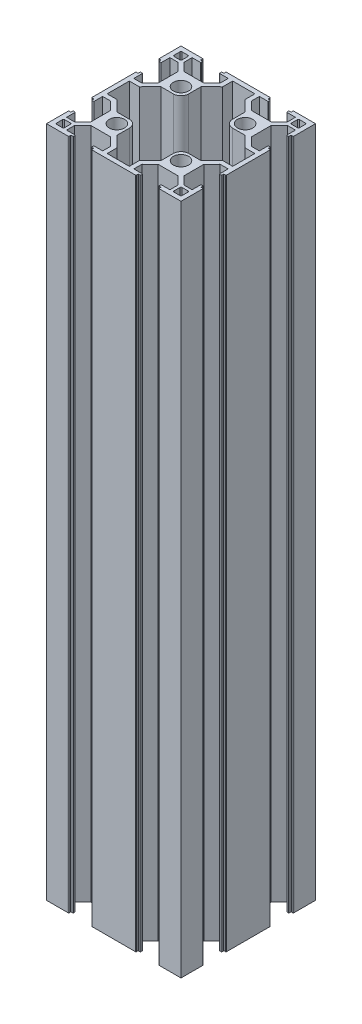
SolidWorks part; units mm, degrees
ref_plane "Front Plane" through (0, 0, 0) normal (0, 0, 1) x (1, 0, 0)
ref_plane "Top Plane" through (0, 0, 0) normal (0, 1, 0) x (1, 0, 0)
ref_plane "Right Plane" through (0, 0, 0) normal (1, 0, 0) x (0, 0, -1)
sketch "Sketch1" plane through (0, 0, 0) normal (0, 1, 0) x (1, 0, 0)
  line L0 (0, 30) -> (0, -30) construction
  line L1 (-30, -30) -> (30, -30)
  line L2 (-30, -30) -> (-30, 30)
  line L3 (-30, 30) -> (30, 30)
  line L4 (30, -30) -> (30, 30)
  line L5 (-30, -30) -> (30, 30) construction
  line L6 (-30, 30) -> (30, -30) construction
  line L7 (-30, 0) -> (30, 0) construction
  line L8 (-23.05, -28) -> (-6.95, -28)
  line L9 (-6.95, -28) -> (-6.95, -24.4)
  line L10 (-6.95, -24.4) -> (-10.615, -20.8)
  line L11 (-10.615, -20.8) -> (-19.385, -20.8)
  line L12 (-19.385, -20.8) -> (-23.05, -24.4)
  line L13 (-23.05, -24.4) -> (-23.05, -28)
  line L14 (10.615, -20.8) -> (19.385, -20.8)
  line L15 (6.95, -24.4) -> (10.615, -20.8)
  line L16 (6.95, -28) -> (6.95, -24.4)
  line L17 (23.05, -28) -> (6.95, -28)
  line L18 (23.05, -24.4) -> (23.05, -28)
  line L19 (19.385, -20.8) -> (23.05, -24.4)
  line L20 (19.385, 20.8) -> (23.05, 24.4)
  line L21 (23.05, 24.4) -> (23.05, 28)
  line L22 (23.05, 28) -> (6.95, 28)
  line L23 (6.95, 28) -> (6.95, 24.4)
  line L24 (6.95, 24.4) -> (10.615, 20.8)
  line L25 (10.615, 20.8) -> (19.385, 20.8)
  line L26 (-23.05, 24.4) -> (-23.05, 28)
  line L27 (-19.385, 20.8) -> (-23.05, 24.4)
  line L28 (-10.615, 20.8) -> (-19.385, 20.8)
  line L29 (-6.95, 24.4) -> (-10.615, 20.8)
  line L30 (-6.95, 28) -> (-6.95, 24.4)
  line L31 (-23.05, 28) -> (-6.95, 28)
  line L32 (-20.8, 19.385) -> (-24.4, 23.05)
  line L33 (-24.4, 23.05) -> (-28, 23.05)
  line L34 (-28, 23.05) -> (-28, 6.95)
  line L35 (-28, 6.95) -> (-24.4, 6.95)
  line L36 (-24.4, 6.95) -> (-20.8, 10.615)
  line L37 (-20.8, 10.615) -> (-20.8, 19.385)
  line L38 (-24.4, -23.05) -> (-28, -23.05)
  line L39 (-20.8, -19.385) -> (-24.4, -23.05)
  line L40 (-20.8, -10.615) -> (-20.8, -19.385)
  line L41 (-24.4, -6.95) -> (-20.8, -10.615)
  line L42 (-28, -6.95) -> (-24.4, -6.95)
  line L43 (-28, -23.05) -> (-28, -6.95)
  line L44 (20.8, -19.385) -> (24.4, -23.05)
  line L45 (24.4, -23.05) -> (28, -23.05)
  line L46 (28, -23.05) -> (28, -6.95)
  line L47 (28, -6.95) -> (24.4, -6.95)
  line L48 (24.4, -6.95) -> (20.8, -10.615)
  line L49 (20.8, -10.615) -> (20.8, -19.385)
  line L50 (24.4, 23.05) -> (28, 23.05)
  line L51 (20.8, 19.385) -> (24.4, 23.05)
  line L52 (20.8, 10.615) -> (20.8, 19.385)
  line L53 (24.4, 6.95) -> (20.8, 10.615)
  line L54 (28, 6.95) -> (24.4, 6.95)
  line L55 (28, 23.05) -> (28, 6.95)
  point P0 (0, 0)
  dimension "D1" = 60
  dimension "D2" = 16.1
  dimension "D3" = 8.77
  dimension "D4" = 3.6
  dimension "D5" = 7.2
  dimension "D6" = 2
  dimension "D7" = 6.95
extrude "Boss-Extrude1" add sketch "Sketch1" along normal blind 300
sketch "Sketch2" plane through (0, 300, 0) normal (0, 1, 0) x (1, 0, 0)
  line L0 (-19.1, -28) -> (-19.1, -29)
  line L1 (-23.05, -28) -> (-6.95, -28) construction
  line L2 (-30, -30) -> (30, -30) construction
  line L3 (-10.9, -28) -> (-10.9, -29)
  line L4 (-10.9, -29) -> (-9.9, -29)
  line L5 (-9.9, -29) -> (-9.9, -30)
  line L6 (-19.1, -29) -> (-20.1, -29)
  line L7 (-20.1, -29) -> (-20.1, -30)
  line L8 (-19.1, -28) -> (-10.9, -28)
  line L9 (-20.1, -30) -> (-9.9, -30)
  dimension "D1" = 8.2
  dimension "D2" = 3.95
  dimension "D3" = 1
  dimension "D4" = 1
extrude "Cut-Extrude1" cut sketch "Sketch2" against normal through all
mirror "Mirror1" about plane through (0, 0, 0) normal (1, 0, 0) of "Cut-Extrude1"
ref_axis "Axis1" through (0, 1050, 0) along (0, -1, 0)
pattern_circular "CirPattern1" count 4 over 360 about axis through (0, 1050, 0) along (0, -1, 0) of "Cut-Extrude1", "Mirror1"
sketch "Sketch4" plane through (0, 300, 0) normal (0, 1, 0) x (1, 0, 0)
  line L0 (19.385, 18.8) -> (9.797, 18.8) construction
  line L1 (-18.8, 18.8) -> (-18.8, 9.797)
  line L2 (18.8, -19.385) -> (18.8, -9.797) construction
  line L3 (28, 4.95) -> (28, -4.95)
  line L4 (-18.8, -9.797) -> (-18.8, -19.385) construction
  line L5 (4.95, -28) -> (-4.95, -28)
  line L6 (-9.797, 18.8) -> (-9.797, 13.197)
  line L7 (-28, -4.95) -> (-28, 4.95)
  line L8 (-18.8, 9.797) -> (-23.5611, 4.95)
  line L9 (-23.5611, 4.95) -> (-28, 4.95)
  line L10 (18.8, 18.8) -> (9.797, 18.8)
  line L11 (9.797, 18.8) -> (4.95, 23.5611)
  line L12 (4.95, 23.5611) -> (4.95, 28)
  line L13 (4.95, 28) -> (4.95, 28)
  line L14 (4.95, 28) -> (4.95, 28)
  line L15 (4.95, 28) -> (4.95, 28)
  line L16 (4.95, 28) -> (4.95, 28)
  line L17 (4.95, 28) -> (-4.95, 28)
  line L18 (-4.95, 28) -> (-4.95, 28)
  line L19 (-4.95, 28) -> (-4.95, 28)
  line L20 (-4.95, 28) -> (-4.95, 28)
  line L21 (-4.95, 28) -> (-4.95, 28)
  line L22 (-4.95, 28) -> (-4.95, 23.5611)
  line L23 (-4.95, 23.5611) -> (-9.797, 18.8)
  line L24 (-9.797, 18.8) -> (-18.8, 18.8)
  line L25 (28, 4.95) -> (23.5611, 4.95)
  line L26 (23.5611, 4.95) -> (18.8, 9.797)
  line L27 (18.8, 9.797) -> (18.8, 18.8)
  line L28 (18.8, -18.8) -> (18.8, -9.797)
  line L29 (18.8, -9.797) -> (23.5611, -4.95)
  line L30 (23.5611, -4.95) -> (28, -4.95)
  line L31 (4.95, -28) -> (4.95, -23.5611)
  line L32 (4.95, -23.5611) -> (9.797, -18.8)
  line L33 (9.797, -18.8) -> (18.8, -18.8)
  line L34 (-18.8, -18.8) -> (-9.797, -18.8)
  line L35 (-9.797, -18.8) -> (-4.95, -23.5611)
  line L36 (-4.95, -23.5611) -> (-4.95, -28)
  line L37 (-28, -4.95) -> (-23.5611, -4.95)
  line L38 (-23.5611, -4.95) -> (-18.8, -9.797)
  line L39 (-18.8, -9.797) -> (-18.8, -18.8)
  line L40 (-9.797, 18.8) -> (-19.385, 18.8) construction
  line L41 (-18.8, 19.385) -> (-18.8, 9.797) construction
  line L42 (18.8, 9.797) -> (18.8, 19.385) construction
  line L43 (9.797, -18.8) -> (19.385, -18.8) construction
  line L44 (-19.385, -18.8) -> (-9.797, -18.8) construction
  line L45 (-13.197, 9.797) -> (-18.8, 9.797)
  line L46 (9.797, 18.8) -> (9.797, 13.197)
  line L47 (13.197, 9.797) -> (18.8, 9.797)
  line L48 (-18.8, -9.797) -> (-13.197, -9.797)
  line L49 (-9.797, -13.197) -> (-9.797, -18.8)
  line L50 (9.797, -18.8) -> (9.797, -13.197)
  line L51 (13.197, -9.797) -> (18.8, -9.797)
  line L52 (-27.5, -28) -> (-24.9, -28)
  line L53 (24.9, -28) -> (27.5, -28)
  line L54 (24.4, -27.5) -> (24.4, -24.9)
  line L55 (24.9, -24.4) -> (27.5, -24.4)
  line L56 (28, -27.5) -> (28, -24.9)
  line L57 (24.4, -28) -> (28, -24.4) construction
  line L58 (24.4, -24.4) -> (28, -28) construction
  line L59 (-28, -24.9) -> (-28, -27.5)
  line L60 (-27.5, -24.4) -> (-24.9, -24.4)
  line L61 (-24.4, -24.9) -> (-24.4, -27.5)
  line L62 (-28, 27.5) -> (-28, 24.9)
  line L63 (-24.9, 28) -> (-27.5, 28)
  line L64 (-24.4, 27.5) -> (-24.4, 24.9)
  line L65 (-24.9, 24.4) -> (-27.5, 24.4)
  line L66 (27.5, 28) -> (24.9, 28)
  line L67 (28, 24.9) -> (28, 27.5)
  line L68 (27.5, 24.4) -> (24.9, 24.4)
  line L69 (24.4, 24.9) -> (24.4, 27.5)
  line L116 (28, 19.1) -> (29, 19.1)
  line L117 (29, 19.1) -> (29, 20.1)
  line L118 (29, 20.1) -> (30, 20.1)
  line L119 (30, 20.1) -> (30, 30)
  line L120 (30, 30) -> (20.1, 30)
  line L121 (20.1, 30) -> (20.1, 29)
  line L122 (20.1, 29) -> (19.1, 29)
  line L123 (19.1, 29) -> (19.1, 28)
  line L124 (19.1, 28) -> (23.05, 28)
  line L125 (23.05, 28) -> (23.05, 24.4)
  line L126 (23.05, 24.4) -> (19.385, 20.8)
  line L127 (19.385, 20.8) -> (10.615, 20.8)
  line L128 (10.615, 20.8) -> (6.95, 24.4)
  line L129 (6.95, 24.4) -> (6.95, 28)
  line L130 (6.95, 28) -> (10.9, 28)
  line L131 (10.9, 28) -> (10.9, 29)
  line L132 (10.9, 29) -> (9.9, 29)
  line L133 (9.9, 29) -> (9.9, 30)
  line L134 (9.9, 30) -> (-9.9, 30)
  line L135 (-9.9, 30) -> (-9.9, 29)
  line L136 (-9.9, 29) -> (-10.9, 29)
  line L137 (-10.9, 29) -> (-10.9, 28)
  line L138 (-10.9, 28) -> (-6.95, 28)
  line L139 (-6.95, 28) -> (-6.95, 24.4)
  line L140 (-6.95, 24.4) -> (-10.615, 20.8)
  line L141 (-10.615, 20.8) -> (-19.385, 20.8)
  line L142 (-19.385, 20.8) -> (-23.05, 24.4)
  line L143 (-23.05, 24.4) -> (-23.05, 28)
  line L144 (-23.05, 28) -> (-19.1, 28)
  line L145 (-19.1, 28) -> (-19.1, 29)
  line L146 (-19.1, 29) -> (-20.1, 29)
  line L147 (-20.1, 29) -> (-20.1, 30)
  line L148 (-20.1, 30) -> (-30, 30)
  line L149 (-30, 30) -> (-30, 20.1)
  line L150 (-30, 20.1) -> (-29, 20.1)
  line L151 (-29, 20.1) -> (-29, 19.1)
  line L152 (-29, 19.1) -> (-28, 19.1)
  line L153 (-28, 19.1) -> (-28, 23.05)
  line L154 (-28, 23.05) -> (-24.4, 23.05)
  line L155 (-24.4, 23.05) -> (-20.8, 19.385)
  line L156 (-20.8, 19.385) -> (-20.8, 10.615)
  line L157 (-20.8, 10.615) -> (-24.4, 6.95)
  line L158 (-24.4, 6.95) -> (-28, 6.95)
  line L159 (-28, 6.95) -> (-28, 10.9)
  line L160 (-28, 10.9) -> (-29, 10.9)
  line L161 (-29, 10.9) -> (-29, 9.9)
  line L162 (-29, 9.9) -> (-30, 9.9)
  line L163 (-30, 9.9) -> (-30, -9.9)
  line L164 (-30, -9.9) -> (-29, -9.9)
  line L165 (-29, -9.9) -> (-29, -10.9)
  line L166 (-29, -10.9) -> (-28, -10.9)
  line L167 (-28, -10.9) -> (-28, -6.95)
  line L168 (-28, -6.95) -> (-24.4, -6.95)
  line L169 (-24.4, -6.95) -> (-20.8, -10.615)
  line L170 (-20.8, -10.615) -> (-20.8, -19.385)
  line L171 (-20.8, -19.385) -> (-24.4, -23.05)
  line L172 (-24.4, -23.05) -> (-28, -23.05)
  line L173 (-28, -23.05) -> (-28, -19.1)
  line L174 (-28, -19.1) -> (-29, -19.1)
  line L175 (-29, -19.1) -> (-29, -20.1)
  line L176 (-29, -20.1) -> (-30, -20.1)
  line L177 (-30, -20.1) -> (-30, -30)
  line L178 (-30, -30) -> (-20.1, -30)
  line L179 (-20.1, -30) -> (-20.1, -29)
  line L180 (-20.1, -29) -> (-19.1, -29)
  line L181 (-19.1, -29) -> (-19.1, -28)
  line L182 (-19.1, -28) -> (-23.05, -28)
  line L183 (-23.05, -28) -> (-23.05, -24.4)
  line L184 (-23.05, -24.4) -> (-19.385, -20.8)
  line L185 (-19.385, -20.8) -> (-10.615, -20.8)
  line L186 (-10.615, -20.8) -> (-6.95, -24.4)
  line L187 (-6.95, -24.4) -> (-6.95, -28)
  line L188 (-6.95, -28) -> (-10.9, -28)
  line L189 (-10.9, -28) -> (-10.9, -29)
  line L190 (-10.9, -29) -> (-9.9, -29)
  line L191 (-9.9, -29) -> (-9.9, -30)
  line L192 (-9.9, -30) -> (9.9, -30)
  line L193 (9.9, -30) -> (9.9, -29)
  line L194 (9.9, -29) -> (10.9, -29)
  line L195 (10.9, -29) -> (10.9, -28)
  line L196 (10.9, -28) -> (6.95, -28)
  line L197 (6.95, -28) -> (6.95, -24.4)
  line L198 (6.95, -24.4) -> (10.615, -20.8)
  line L199 (10.615, -20.8) -> (19.385, -20.8)
  line L200 (19.385, -20.8) -> (23.05, -24.4)
  line L201 (23.05, -24.4) -> (23.05, -28)
  line L202 (23.05, -28) -> (19.1, -28)
  line L203 (19.1, -28) -> (19.1, -29)
  line L204 (19.1, -29) -> (20.1, -29)
  line L205 (20.1, -29) -> (20.1, -30)
  line L206 (20.1, -30) -> (30, -30)
  line L207 (30, -30) -> (30, -20.1)
  line L208 (30, -20.1) -> (29, -20.1)
  line L209 (29, -20.1) -> (29, -19.1)
  line L210 (29, -19.1) -> (28, -19.1)
  line L211 (28, -19.1) -> (28, -23.05)
  line L212 (28, -23.05) -> (24.4, -23.05)
  line L213 (24.4, -23.05) -> (20.8, -19.385)
  line L214 (20.8, -19.385) -> (20.8, -10.615)
  line L215 (20.8, -10.615) -> (24.4, -6.95)
  line L216 (24.4, -6.95) -> (28, -6.95)
  line L217 (28, -6.95) -> (28, -10.9)
  line L218 (28, -10.9) -> (29, -10.9)
  line L219 (29, -10.9) -> (29, -9.9)
  line L220 (29, -9.9) -> (30, -9.9)
  line L221 (30, -9.9) -> (30, 9.9)
  line L222 (30, 9.9) -> (29, 9.9)
  line L223 (29, 9.9) -> (29, 10.9)
  line L224 (29, 10.9) -> (28, 10.9)
  line L225 (28, 10.9) -> (28, 6.95)
  line L226 (28, 6.95) -> (24.4, 6.95)
  line L227 (24.4, 6.95) -> (20.8, 10.615)
  line L228 (20.8, 10.615) -> (20.8, 19.385)
  line L229 (20.8, 19.385) -> (24.4, 23.05)
  line L230 (24.4, 23.05) -> (28, 23.05)
  line L231 (28, 23.05) -> (28, 19.1)
  line L232 (28, 19.1) -> (29, 19.1)
  line L233 (29, 19.1) -> (29, 20.1)
  line L234 (29, 20.1) -> (30, 20.1)
  line L235 (30, 20.1) -> (30, 30)
  line L236 (30, 30) -> (20.1, 30)
  line L237 (20.1, 30) -> (20.1, 29)
  line L238 (20.1, 29) -> (19.1, 29)
  line L239 (19.1, 29) -> (19.1, 28)
  line L240 (19.1, 28) -> (23.05, 28)
  line L241 (23.05, 28) -> (23.05, 24.4)
  line L242 (23.05, 24.4) -> (19.385, 20.8)
  line L243 (19.385, 20.8) -> (10.615, 20.8)
  line L244 (10.615, 20.8) -> (6.95, 24.4)
  line L245 (6.95, 24.4) -> (6.95, 28)
  line L246 (6.95, 28) -> (10.9, 28)
  line L247 (10.9, 28) -> (10.9, 29)
  line L248 (10.9, 29) -> (9.9, 29)
  line L249 (9.9, 29) -> (9.9, 30)
  line L250 (9.9, 30) -> (-9.9, 30)
  line L251 (-9.9, 30) -> (-9.9, 29)
  line L252 (-9.9, 29) -> (-10.9, 29)
  line L253 (-10.9, 29) -> (-10.9, 28)
  line L254 (-10.9, 28) -> (-6.95, 28)
  line L255 (-6.95, 28) -> (-6.95, 24.4)
  line L256 (-6.95, 24.4) -> (-10.615, 20.8)
  line L257 (-10.615, 20.8) -> (-19.385, 20.8)
  line L258 (-19.385, 20.8) -> (-23.05, 24.4)
  line L259 (-23.05, 24.4) -> (-23.05, 28)
  line L260 (-23.05, 28) -> (-19.1, 28)
  line L261 (-19.1, 28) -> (-19.1, 29)
  line L262 (-19.1, 29) -> (-20.1, 29)
  line L263 (-20.1, 29) -> (-20.1, 30)
  line L264 (-20.1, 30) -> (-30, 30)
  line L265 (-30, 30) -> (-30, 20.1)
  line L266 (-30, 20.1) -> (-29, 20.1)
  line L267 (-29, 20.1) -> (-29, 19.1)
  line L268 (-29, 19.1) -> (-28, 19.1)
  line L269 (-28, 19.1) -> (-28, 23.05)
  line L270 (-28, 23.05) -> (-24.4, 23.05)
  line L271 (-24.4, 23.05) -> (-20.8, 19.385)
  line L272 (-20.8, 19.385) -> (-20.8, 10.615)
  line L273 (-20.8, 10.615) -> (-24.4, 6.95)
  line L274 (-24.4, 6.95) -> (-28, 6.95)
  line L275 (-28, 6.95) -> (-28, 10.9)
  line L276 (-28, 10.9) -> (-29, 10.9)
  line L277 (-29, 10.9) -> (-29, 9.9)
  line L278 (-29, 9.9) -> (-30, 9.9)
  line L279 (-30, 9.9) -> (-30, -9.9)
  line L280 (-30, -9.9) -> (-29, -9.9)
  line L281 (-29, -9.9) -> (-29, -10.9)
  line L282 (-29, -10.9) -> (-28, -10.9)
  line L283 (-28, -10.9) -> (-28, -6.95)
  line L284 (-28, -6.95) -> (-24.4, -6.95)
  line L285 (-24.4, -6.95) -> (-20.8, -10.615)
  line L286 (-20.8, -10.615) -> (-20.8, -19.385)
  line L287 (-20.8, -19.385) -> (-24.4, -23.05)
  line L288 (-24.4, -23.05) -> (-28, -23.05)
  line L289 (-28, -23.05) -> (-28, -19.1)
  line L290 (-28, -19.1) -> (-29, -19.1)
  line L291 (-29, -19.1) -> (-29, -20.1)
  line L292 (-29, -20.1) -> (-30, -20.1)
  line L293 (-30, -20.1) -> (-30, -30)
  line L294 (-30, -30) -> (-20.1, -30)
  line L295 (-20.1, -30) -> (-20.1, -29)
  line L296 (-20.1, -29) -> (-19.1, -29)
  line L297 (-19.1, -29) -> (-19.1, -28)
  line L298 (-19.1, -28) -> (-23.05, -28)
  line L299 (-23.05, -28) -> (-23.05, -24.4)
  line L300 (-23.05, -24.4) -> (-19.385, -20.8)
  line L301 (-19.385, -20.8) -> (-10.615, -20.8)
  line L302 (-10.615, -20.8) -> (-6.95, -24.4)
  line L303 (-6.95, -24.4) -> (-6.95, -28)
  line L304 (-6.95, -28) -> (-10.9, -28)
  line L305 (-10.9, -28) -> (-10.9, -29)
  line L306 (-10.9, -29) -> (-9.9, -29)
  line L307 (-9.9, -29) -> (-9.9, -30)
  line L308 (-9.9, -30) -> (9.9, -30)
  line L309 (9.9, -30) -> (9.9, -29)
  line L310 (9.9, -29) -> (10.9, -29)
  line L311 (10.9, -29) -> (10.9, -28)
  line L312 (10.9, -28) -> (6.95, -28)
  line L313 (6.95, -28) -> (6.95, -24.4)
  line L314 (6.95, -24.4) -> (10.615, -20.8)
  line L315 (10.615, -20.8) -> (19.385, -20.8)
  line L316 (19.385, -20.8) -> (23.05, -24.4)
  line L317 (23.05, -24.4) -> (23.05, -28)
  line L318 (23.05, -28) -> (19.1, -28)
  line L319 (19.1, -28) -> (19.1, -29)
  line L320 (19.1, -29) -> (20.1, -29)
  line L321 (20.1, -29) -> (20.1, -30)
  line L322 (20.1, -30) -> (30, -30)
  line L323 (30, -30) -> (30, -20.1)
  line L324 (30, -20.1) -> (29, -20.1)
  line L325 (29, -20.1) -> (29, -19.1)
  line L326 (29, -19.1) -> (28, -19.1)
  line L327 (28, -19.1) -> (28, -23.05)
  line L328 (28, -23.05) -> (24.4, -23.05)
  line L329 (24.4, -23.05) -> (20.8, -19.385)
  line L330 (20.8, -19.385) -> (20.8, -10.615)
  line L331 (20.8, -10.615) -> (24.4, -6.95)
  line L332 (24.4, -6.95) -> (28, -6.95)
  line L333 (28, -6.95) -> (28, -10.9)
  line L334 (28, -10.9) -> (29, -10.9)
  line L335 (29, -10.9) -> (29, -9.9)
  line L336 (29, -9.9) -> (30, -9.9)
  line L337 (30, -9.9) -> (30, 9.9)
  line L338 (30, 9.9) -> (29, 9.9)
  line L339 (29, 9.9) -> (29, 10.9)
  line L340 (29, 10.9) -> (28, 10.9)
  line L341 (28, 10.9) -> (28, 6.95)
  line L342 (28, 6.95) -> (24.4, 6.95)
  line L343 (24.4, 6.95) -> (20.8, 10.615)
  line L344 (20.8, 10.615) -> (20.8, 19.385)
  line L345 (20.8, 19.385) -> (24.4, 23.05)
  line L346 (24.4, 23.05) -> (28, 23.05)
  line L347 (28, 23.05) -> (28, 19.1)
  circle A0 centre (14.2985, 14.2985) radius 3.4
  arc A1 (13.197, -9.797) -> (9.797, -13.197) centre (13.197, -13.197) ccw
  arc A2 (-9.797, -13.197) -> (-13.197, -9.797) centre (-13.197, -13.197) ccw
  arc A3 (13.197, 9.797) -> (9.797, 13.197) centre (13.197, 13.197) cw
  arc A4 (-9.797, 13.197) -> (-13.197, 9.797) centre (-13.197, 13.197) cw
  circle A5 centre (14.2985, -14.2985) radius 3.4
  circle A6 centre (-14.2985, -14.2985) radius 3.4
  circle A7 centre (-14.2985, 14.2985) radius 3.4
  arc A8 (24.4, -27.5) -> (24.9, -28) centre (24.9, -27.5) ccw
  arc A9 (28, -27.5) -> (27.5, -28) centre (27.5, -27.5) cw
  arc A10 (28, -24.9) -> (27.5, -24.4) centre (27.5, -24.9) ccw
  arc A11 (24.4, -24.9) -> (24.9, -24.4) centre (24.9, -24.9) cw
  arc A12 (-27.5, -28) -> (-28, -27.5) centre (-27.5, -27.5) cw
  arc A13 (-27.5, -24.4) -> (-28, -24.9) centre (-27.5, -24.9) ccw
  arc A14 (-24.9, -24.4) -> (-24.4, -24.9) centre (-24.9, -24.9) cw
  arc A15 (-24.9, -28) -> (-24.4, -27.5) centre (-24.9, -27.5) ccw
  arc A16 (-28, 27.5) -> (-27.5, 28) centre (-27.5, 27.5) cw
  arc A17 (-24.4, 27.5) -> (-24.9, 28) centre (-24.9, 27.5) ccw
  arc A18 (-24.4, 24.9) -> (-24.9, 24.4) centre (-24.9, 24.9) cw
  arc A19 (-28, 24.9) -> (-27.5, 24.4) centre (-27.5, 24.9) ccw
  arc A20 (27.5, 28) -> (28, 27.5) centre (27.5, 27.5) cw
  arc A21 (27.5, 24.4) -> (28, 24.9) centre (27.5, 24.9) ccw
  arc A22 (24.9, 24.4) -> (24.4, 24.9) centre (24.9, 24.9) cw
  arc A23 (24.9, 28) -> (24.4, 27.5) centre (24.9, 27.5) ccw
  point P102 (26.2, -26.2)
  point P104 (14.2985, 18.8)
  point P106 (18.8, 14.2985)
  point P140 (0, 0)
  point P239 (0, 0)
  dimension "D3" = 6.8
  dimension "D4" = 3.4
  dimension "D6" = 0.5
  dimension "D1" = 0
  dimension "D2" = 2
  dimension "D5" = 4
  dimension "D7" = 4
extrude "Cut-Extrude2" cut sketch "Sketch4" against normal blind 1000 contours L6 A4 L45 L8 L9 L7 L37 L38 L48 A2 L49 L35 L36 L5 L31 L32 L50 A1 L51 L29 L30 L3 L25 L26 L47 A3 L46 L11 L12 L17 L22 L23 | A7 | A0 | L66 A23 L69 A22 L68 A21 L67 A20 | L62 A19 L65 A18 L64 A17 L63 A16 | L52 A15 L61 A14 L60 A13 L59 A12 | A11 L54 A8 L53 A9 L56 A10 L55 | A6 | A5 region at (0, 300, 0) region at (-26.2, 300, 26.2) region at (26.2, 300, 26.2) region at (-26.2, 300, -26.2) region at (26.2, 300, -26.2) region at (14.2985, 300, -14.2985) region at (-14.2985, 300, -14.2985)
fillet "Fillet1" radius 0.2 16 edges at (28, 150, -19.1) (30, 150, -20.1) (29, 150, -20.1) (29, 150, -19.1) (28, 150, 10.9) (29, 150, 9.9) (28, 150, 19.1) (29, 150, 20.1) (30, 150, 20.1) (29, 150, 19.1) (29, 150, 10.9) (30, 150, 9.9) (30, 150, -9.9) (29, 150, -9.9) (29, 150, -10.9) (28, 150, -10.9)
fillet "Fillet2" radius 0.2 20 edges at (-20.1, 0, -29.5) (-20.1, 300, -29.5) (-20.1, 150, -29) (-19.6, 0, -29) (-19.1, 150, -29) (-19.6, 300, -29) (-9.9, 150, -30) (-10.9, 150, -28) (-10.9, 150, -29) (-9.9, 150, -29) (19.1, 150, -28) (19.1, 150, -29) (20.1, 150, -29) (20.1, 150, -30) (10.9, 150, -28) (10.9, 150, -29) (9.9, 150, -29) (9.9, 150, -30) (-19.1, 150, -28) (-20.1, 150, -30)
fillet "Fillet3" radius 0.2 14 edges at (-29, 150, 9.9) (-29, 150, -20.1) (-30, 150, -20.1) (-29, 150, -19.1) (-28, 150, -10.9) (-29, 150, -10.9) (-29, 150, -9.9) (-30, 150, -9.9) (-29, 150, 10.9) (-30, 150, 9.9) (-28, 150, 19.1) (-29, 150, 19.1) (-29, 150, 20.1) (-30, 150, 20.1)
fillet "Fillet4" radius 0.2 16 edges at (-19.1, 150, 28) (10.9, 150, 28) (19.1, 150, 28) (20.1, 150, 29) (-10.9, 150, 28) (-9.9, 150, 29) (9.9, 150, 29) (-20.1, 150, 29) (19.1, 150, 29) (20.1, 150, 30) (10.9, 150, 29) (9.9, 150, 30) (-9.9, 150, 30) (-10.9, 150, 29) (-19.1, 150, 29) (-20.1, 150, 30)
